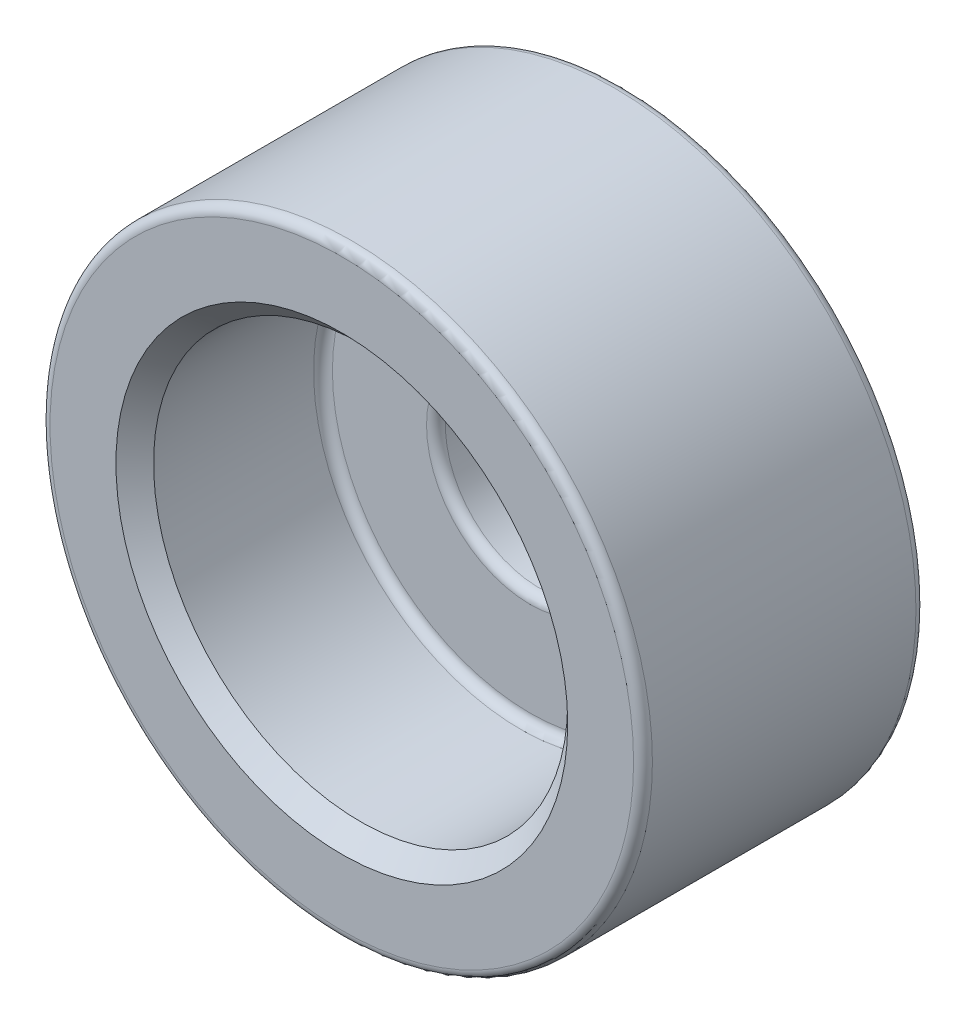
SolidWorks part; units mm, degrees
ref_plane "Alzado" through (0, 0, 0) normal (0, 0, 1) x (1, 0, 0)
ref_plane "Planta" through (0, 0, 0) normal (0, 1, 0) x (1, 0, 0)
ref_plane "Vista lateral" through (0, 0, 0) normal (1, 0, 0) x (0, 0, -1)
sketch "Croquis1" plane through (0, 0, 0) normal (0, 0, 1) x (1, 0, 0)
  circle A0 centre (0, 0) radius 16
  dimension "D1" = 32
extrude "Saliente-Extruir1" add sketch "Croquis1" along normal blind 15
sketch "Croquis2" plane through (0, 0, 15) normal (0, 0, 1) x (1, 0, 0)
  circle A0 centre (0, 0) radius 11
  dimension "D1" = 22
extrude "Cortar-Extruir1" cut sketch "Croquis2" against normal blind 10
sketch "Croquis3" plane through (0, 0, 5) normal (0, 0, 1) x (1, 0, 0)
  circle A0 centre (0, 0) radius 5
  dimension "D1" = 10
extrude "Cortar-Extruir2" cut sketch "Croquis3" against normal up to surface (5 mm away) up to face at (16, 0, 0)
chamfer "Chaflán1" distance 1 angle 45 1 edges at (11, 0, 15)
fillet "Redondeo1" radius 0.5 5 edges at (16, 0, 15) (16, 0, 0) (5, 0, 0) (5, 0, 5) (11, 0, 5)
